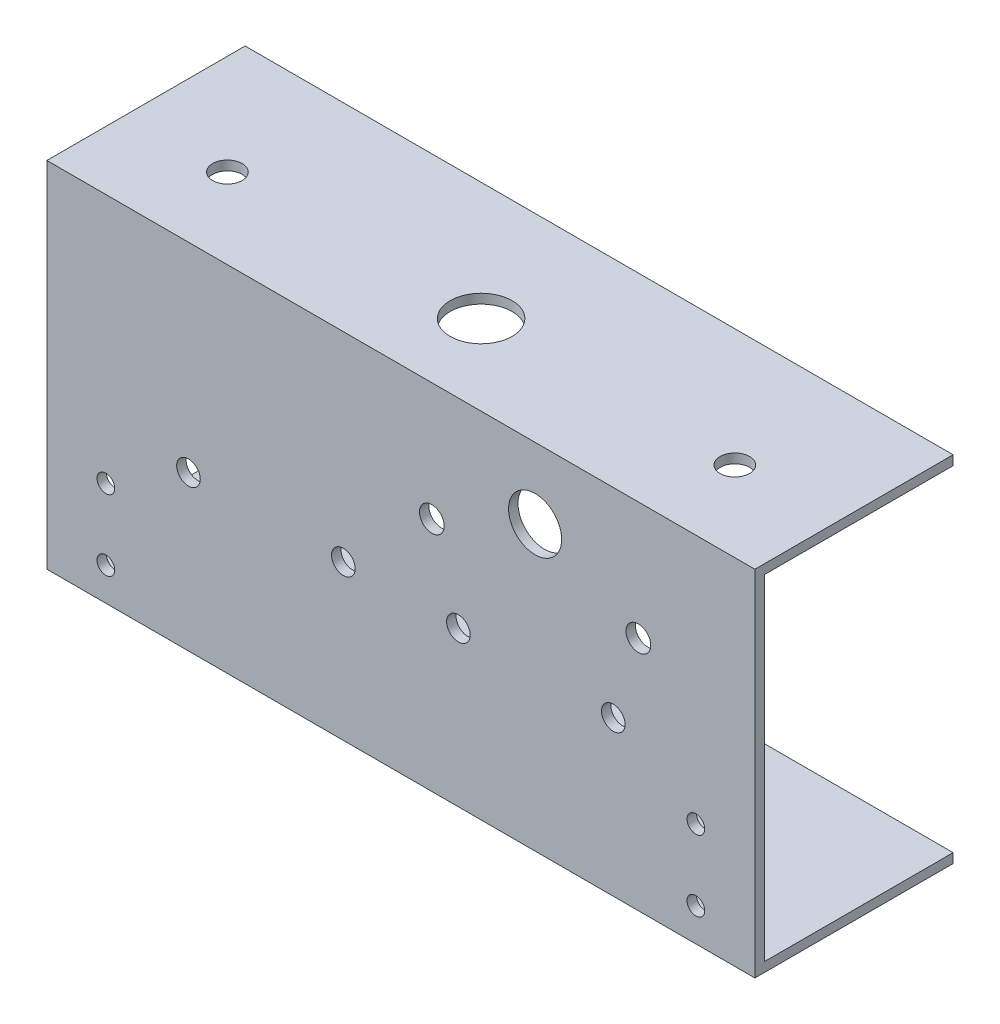
SolidWorks part; units mm, degrees
ref_plane "Front Plane" through (0, 0, 0) normal (0, 0, 1) x (1, 0, 0)
ref_plane "Top Plane" through (0, 0, 0) normal (0, 1, 0) x (1, 0, 0)
ref_plane "Right Plane" through (0, 0, 0) normal (1, 0, 0) x (0, 0, -1)
sketch "Sketch1" plane through (0, 0, 0) normal (0, 1, 0) x (1, 0, 0)
  line L0 (0, -16.0011) -> (0, 16.0011) construction
  line L14 (-60, -12) -> (60, -12)
  line L15 (-60, -12) -> (-60, 20)
  line L16 (-60, 20) -> (60, 20)
  line L17 (60, -12) -> (60, 20)
  circle A0 centre (0, 0) radius 5.25
  circle A1 centre (-43, 0) radius 2.5
  circle A2 centre (43, 0) radius 2.5
  point P0 (0, 0)
  dimension "D3" = 10.5
  dimension "D4" = 43
  dimension "D5" = 5
  dimension "D8" = 12
  dimension "D1" = 20
  dimension "D2" = 12
  dimension "D6" = 120
  dimension "D7" = 60
other "AlignGroup1"
other "AlignGroup2"
extrude "Boss-Extrude1" add sketch "Sketch1" along normal blind 1.6
sketch "Sketch3" plane through (0, 0, 0) normal (0, -1, 0) x (1, 0, 0)
  line L1 (-60, 12) -> (60, 12)
  line L2 (-60, 12) -> (-60, 13.6)
  line L3 (-60, 13.6) -> (60, 13.6)
  line L4 (60, 12) -> (60, 13.6)
  dimension "D1" = 1.6
extrude "Boss-Extrude3" add sketch "Sketch3" against normal blind 60
ref_plane "Plane1" through (0, 30, 0) normal (0, 1, 0) x (1, 0, 0)
mirror "Mirror1" about plane through (0, 30, 0) normal (0, 1, 0) of "Boss-Extrude1"
sketch "Sketch4" plane through (0, 0, 13.6) normal (0, 0, 1) x (1, 0, 0)
  line L0 (60, 0) -> (-60, 0) construction
  line L1 (60, 60) -> (-60, 60) construction
  line L2 (22.75, 48) -> (22.75, 5.2725)
  circle A0 centre (5.25, 40) radius 2.1
  circle A1 centre (22.75, 48) radius 4.5
  circle A2 centre (40.25, 40) radius 2.1
  point P6 (0, 60)
  dimension "D1" = 4.2
  dimension "D4" = 9
  dimension "D2" = 40
  dimension "D3" = 5.25
  dimension "D5" = 8
  dimension "D6" = 17.5
extrude "Cut-Extrude1" cut sketch "Sketch4" against normal blind 2 contours A0 | A1 | A2 region at (5.25, 40, 13.6) region at (25.842, 44.908, 13.6) region at (40.25, 40, 13.6)
sketch "Sketch6" plane through (124.2445, 40.7, 12) normal (0, 0, 1) x (1, 0, 0)
  line L0 (-184.2445, -14.5) -> (-64.2445, -14.5)
  line L2 (-164.7445, -39.1) -> (-164.7445, -14.5)
  line L3 (-129.4945, -39.1) -> (-129.4945, -14.5)
  line L4 (-118.9945, -39.1) -> (-118.9945, -14.5)
  line L5 (-83.7445, -39.1) -> (-83.7445, -14.5)
  line L6 (-124.2445, -39.1) -> (-124.2445, -14.5)
  line L16 (-64.2445, -39.1) -> (-64.2445, 17.7)
  line L17 (-64.2445, 17.7) -> (-184.2445, 17.7)
  line L18 (-184.2445, 17.7) -> (-184.2445, -39.1)
  line L19 (-184.2445, -39.1) -> (-64.2445, -39.1)
  circle A0 centre (-160.2445, -14.5) radius 2
  circle A1 centre (-133.9945, -14.5) radius 2
  circle A2 centre (-114.4945, -14.5) radius 2
  circle A3 centre (-88.2445, -14.5) radius 2
  dimension "D1" = 4
  dimension "D3" = 4
  dimension "D2" = 4.5
  dimension "D4" = 4.5
extrude "Cut-Extrude2" cut sketch "Sketch6" along normal blind 25 contours A3 | A2 | A1 | A0
sketch "Sketch7" plane through (0, 0, 12) normal (0, 0, -1) x (-1, 0, 0)
  line L1 (0, 28.93) -> (0, -28.93) construction
  circle A0 centre (-50, 17.6) radius 1.5
  circle A1 centre (-50, 5.6) radius 1.5
  circle A2 centre (50, 5.6) radius 1.5
  circle A3 centre (50, 17.6) radius 1.5
  dimension "D1" = 3
  dimension "D2" = 3
extrude "Cut-Extrude4" cut sketch "Sketch7" against normal blind 3
